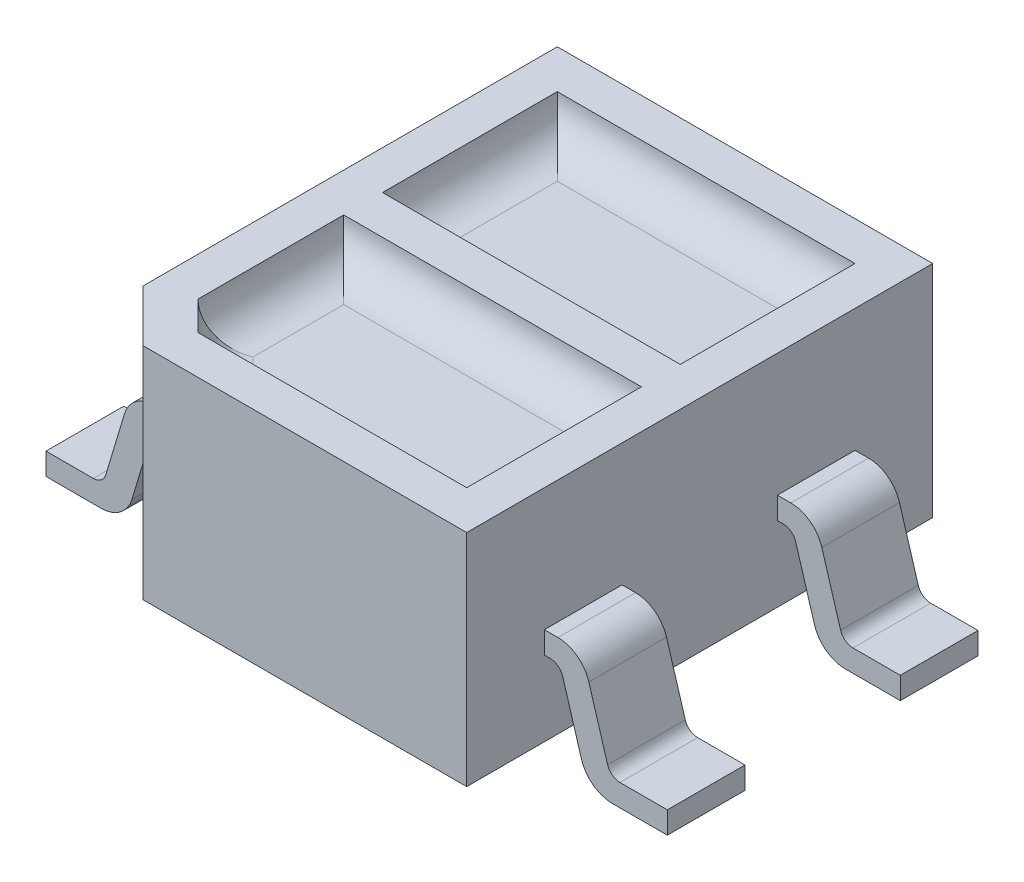
SolidWorks part; units mm, degrees
ref_plane "Спереди" through (0, 0, 0) normal (0, 0, 1) x (1, 0, 0)
ref_plane "Сверху" through (0, 0, 0) normal (0, 1, 0) x (1, 0, 0)
ref_plane "Справа" through (0, 0, 0) normal (1, 0, 0) x (0, 0, -1)
sketch "Эскиз1" plane through (0, 0, 0) normal (0, 1, 0) x (1, 0, 0)
  line L0 (1.45, -1.8) -> (-1.05, -1.8)
  line L1 (-1.45, 1.8) -> (1.45, 1.8)
  line L2 (-1.45, 1.8) -> (-1.45, -1.4)
  line L3 (-1.05, -1.8) -> (-1.45, -1.4)
  line L4 (1.45, 1.8) -> (1.45, -1.8)
  dimension "D2" = 2.9
extrude "Бобышка-Вытянуть1" add sketch "Эскиз1" along normal blind 1.7
sketch "Эскиз2" plane through (0, 1.7, 0) normal (0, 1, 0) x (1, 0, 0)
  line L15 (1.15, 0.15) -> (-1.15, 0.15)
  line L16 (-1.15, -1.2757) -> (-0.9257, -1.5)
  line L17 (1.15, 1.5) -> (-1.15, 1.5)
  line L18 (1.15, 1.5) -> (1.15, 0.15)
  line L19 (-1.15, 1.5) -> (-1.15, 0.15)
  line L20 (1.15, -1.5) -> (-0.9257, -1.5)
  line L21 (-1.15, -0.15) -> (-1.15, -1.2757)
  line L22 (1.15, -0.15) -> (-1.15, -0.15)
  line L23 (1.15, -0.15) -> (1.15, -1.5)
  point P2 (0, 0)
extrude "Вырез-Вытянуть1" cut sketch "Эскиз2" against normal blind 0.3
fillet "Скругление1" radius 0.3 4 edges at (0, 1.4, -0.15) (-1.15, 1.4, -0.825) (0, 1.4, -1.5) (1.15, 1.4, -0.825)
fillet "Скругление2" radius 0.3 5 edges at (0.1121, 1.4, 1.5) (-1.0379, 1.4, 1.3879) (-1.15, 1.4, 0.7129) (0, 1.4, 0.15) (1.15, 1.4, 0.825)
sketch "Эскиз3" plane through (0, 0, 1.8) normal (0, 0, 1) x (1, 0, 0)
  line L0 (1.5914, 0.5089) -> (1.7364, 0.0279)
  line L1 (2.4, -0.15) -> (2.4, 0.02)
  line L2 (2.4, -0.15) -> (1.9758, -0.15)
  line L3 (2.4, 0.02) -> (2.0343, 0.02)
  line L4 (1.45, 1.7) -> (1.45, 0) construction
  line L5 (1.45, 0.58) -> (1.4957, 0.58)
  line L6 (1.45, 0.75) -> (1.5542, 0.75)
  line L7 (1.79, -0.15) -> (1.7958, -0.153)
  line L8 (1.7936, 0.5721) -> (1.9386, 0.0911)
  line L9 (1.45, 0.75) -> (1.45, 0.58)
  line L10 (0, 0) -> (0, 2.8149) construction
  line L11 (-1.45, 0.75) -> (-1.45, 0.58)
  line L12 (-1.7936, 0.5721) -> (-1.9386, 0.0911)
  line L13 (-1.79, -0.15) -> (-1.7958, -0.153)
  line L14 (-1.45, 0.75) -> (-1.5542, 0.75)
  line L15 (-1.45, 0.58) -> (-1.4957, 0.58)
  line L16 (-2.4, 0.02) -> (-2.0343, 0.02)
  line L17 (-2.4, -0.15) -> (-1.9758, -0.15)
  line L18 (-2.4, -0.15) -> (-2.4, 0.02)
  line L19 (-1.5914, 0.5089) -> (-1.7364, 0.0279)
  line L20 (-1.45, 0.75) -> (-1.45, 0.58)
  line L21 (1.45, 0.75) -> (1.45, 0.58)
  arc A0 (2.0343, 0.02) -> (1.9386, 0.0911) centre (2.0343, 0.12) cw
  arc A1 (1.5914, 0.5089) -> (1.4957, 0.58) centre (1.4957, 0.48) ccw
  arc A2 (1.7364, 0.0279) -> (1.9758, -0.15) centre (1.9758, 0.1) ccw
  arc A3 (1.5542, 0.75) -> (1.7936, 0.5721) centre (1.5542, 0.5) cw
  arc A4 (-1.5542, 0.75) -> (-1.7936, 0.5721) centre (-1.5542, 0.5) ccw
  arc A5 (-1.7364, 0.0279) -> (-1.9758, -0.15) centre (-1.9758, 0.1) cw
  arc A6 (-1.5914, 0.5089) -> (-1.4957, 0.58) centre (-1.4957, 0.48) cw
  arc A7 (-2.0343, 0.02) -> (-1.9386, 0.0911) centre (-2.0343, 0.12) ccw
  line M8 (1.45, 0) -> (1.45, 1.7)
  dimension "D1" = 0.1
  dimension "D2" = 0.1
  dimension "D3" = 0.25
extrude "Бобышка-Вытянуть2" add sketch "Эскиз3" against normal blind 3.6 contours A7 L16 L18 L17 A5 L19 A6 L15 L11 L14 A4 L12 | A3 L6 L5 A1 L0 A2 L2 L1 L3 A0 L8 M8 region at (1.8591, 0.2277, 1.8) region at (-1.8591, 0.2277, 1.8)
sketch "Эскиз4" plane through (0, 0.75, 0) normal (0, 1, 0) x (1, 0, 0)
  line L0 (2.4, 1.2) -> (1.45, 1.2)
  line L1 (2.4, 1.8) -> (2.4, -1.8) construction
  line L2 (1.45, -1.8) -> (1.45, 1.8) construction
  line L3 (-2.4, 1.8) -> (-2.4, 1.2)
  line L4 (-1.45, 1.8) -> (-2.4, 1.8)
  line L5 (1.45, 1.8) -> (1.45, -1.8) construction
  line L6 (1.45, 0.6) -> (2.4, 0.6)
  line L7 (2.4, 0.6) -> (2.4, -0.6)
  line L8 (1.45, 1.2) -> (1.45, 1.8)
  line L9 (1.45, 1.8) -> (2.4, 1.8)
  line L10 (2.4, 1.8) -> (2.4, 1.2)
  line L11 (-1.45, 1.2) -> (-1.45, 1.8)
  line L12 (-1.45, 0.6) -> (-2.4, 0.6)
  line L13 (-2.4, 1.2) -> (-1.45, 1.2)
  line L14 (-2.4, -1.2) -> (-1.45, -1.2)
  line L15 (-1.45, -0.6) -> (-2.4, -0.6)
  line L16 (-1.45, -1.2) -> (-1.45, -1.8)
  line L17 (2.4, -1.8) -> (2.4, -1.2)
  line L18 (1.45, -1.8) -> (2.4, -1.8)
  line L19 (1.45, -1.2) -> (1.45, -1.8)
  line L20 (1.45, -0.6) -> (2.4, -0.6)
  line L21 (-1.45, -1.8) -> (-2.4, -1.8)
  line L22 (-2.4, -1.8) -> (-2.4, -1.2)
  line L23 (2.4, -1.2) -> (1.45, -1.2)
  line L24 (1.45, 0.6) -> (1.45, -0.6)
  line L25 (-1.45, 0.6) -> (-1.45, -0.6)
  line L26 (-2.4, 0.6) -> (-2.4, -0.6)
extrude "Вырез-Вытянуть2" cut sketch "Эскиз4" against normal blind 3.6
